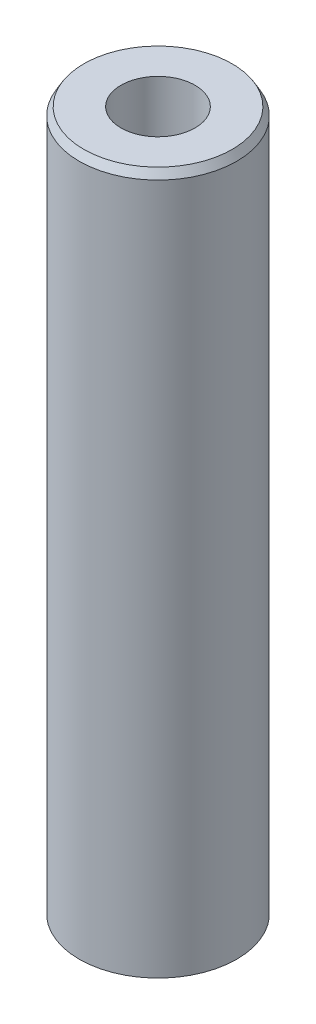
SolidWorks part; units mm, degrees
ref_plane "Front Plane" through (0, 0, 0) normal (0, 0, 1) x (1, 0, 0)
ref_plane "Top Plane" through (0, 0, 0) normal (0, 1, 0) x (1, 0, 0)
ref_plane "Right Plane" through (0, 0, 0) normal (1, 0, 0) x (0, 0, -1)
sketch "Sketch1" plane through (0, 0, 0) normal (0, 1, 0) x (1, 0, 0)
  circle A0 centre (0, 0) radius 27.5
  dimension "SHAFT_OD" = 55
extrude "Boss-Extrude1" add sketch "Sketch1" along normal blind 245.5576
sketch "Sketch2" plane through (0, 0, 0) normal (0, 1, 0) x (1, 0, 0)
  circle A0 centre (0, 0) radius 12.9273
  dimension "BORE_D" = 25.8546
extrude "Cut-Extrude1" cut sketch "Sketch2" along normal through all
chamfer "Chamfer1" distance 2.7843 angle 30 2 edges at (0, 245.5576, 27.5) (0, 0, 27.5) first distance on face at (0, 245.5576, 27.5) first distance on face at (0, 0, 12.9273)
